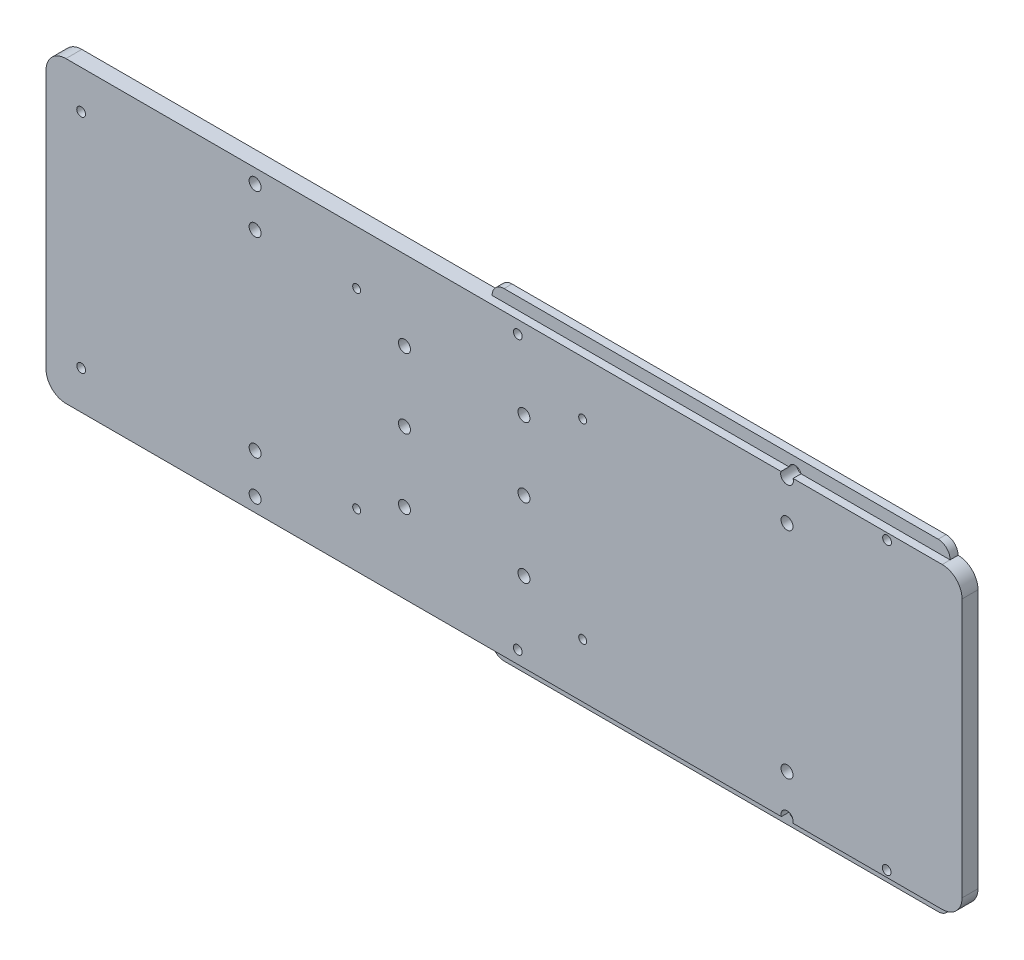
SolidWorks part; units mm, degrees
ref_plane "Plan de face" through (0, 0, 0) normal (0, 0, 1) x (1, 0, 0)
ref_plane "Plan de dessus" through (0, 0, 0) normal (0, 1, 0) x (1, 0, 0)
ref_plane "Plan de droite" through (0, 0, 0) normal (1, 0, 0) x (0, 0, -1)
sketch "Sketch1" plane through (0, 0, 0) normal (0, 0, 1) x (1, 0, 0)
  line L1 (0, 0) -> (230, 0)
  line L2 (0, 0) -> (0, 75)
  line L3 (0, 75) -> (230, 75)
  line L4 (230, 0) -> (230, 75)
  dimension "D1" = 230
  dimension "D2" = 75
extrude "Boss-Extrude1" add sketch "Sketch1" along normal blind 4
sketch "Sketch2" plane through (0, 0, 0) normal (0, 0, -1) x (-1, 0, 0)
  line L0 (-9.0685, 28.6546) -> (-9.0685, 48.2614) construction
  text T0 "BOTTOM"
extrude "Cut-Extrude1" cut sketch "Sketch2" against normal blind 1
fillet "Fillet1" radius 5 4 edges at (0, 0, 2) (230, 0, 2) (0, 75, 2) (230, 75, 2)
sketch "Sketch4" plane through (0, 0, 0) normal (0, 0, -1) x (-1, 0, 0)
  line L0 (-230, 5) -> (-230, 70) construction
  line L1 (-225, 75) -> (-110, 75)
  line L2 (-225, 75) -> (-225, 78)
  line L3 (-225, 78) -> (-110, 78)
  line L4 (-110, 75) -> (-110, 78)
  line L5 (-225, 0) -> (-110, 0)
  line L6 (-225, 0) -> (-225, -3)
  line L7 (-225, -3) -> (-110, -3)
  line L8 (-110, 0) -> (-110, -3)
  dimension "D1" = 3
  dimension "D2" = 3
  dimension "D3" = 120
  dimension "D4" = 120
extrude "Boss-Extrude2" add sketch "Sketch4" against normal blind 2 separate body
fillet "Fillet4" radius 3 1 edges at (225, 78, 1)
fillet "Fillet5" radius 3 2 edges at (110, -3, 1) (225, -3, 1)
fillet "Fillet6" radius 3 1 edges at (110, 78, 1)
sketch "Sketch5" plane through (0, 0, 0) normal (0, 0, -1) x (-1, 0, 0)
  line L0 (0, 70) -> (0, 5) construction
  line L1 (-5, 0) -> (-225, 0) construction
  line L2 (-225, 75) -> (-5, 75) construction
  line L3 (-230, 5) -> (-230, 70) construction
  line L4 (-222, -3) -> (-113, -3) construction
  line L5 (-113, 78) -> (-222, 78) construction
  circle A0 centre (-8.82, 9.65) radius 1.1
  circle A1 centre (-8.82, 65.35) radius 1.1
  circle A2 centre (-118.46, 71.81) radius 1.1
  circle A3 centre (-118.46, 3.19) radius 1.1
  circle A4 centre (-211.07, 1.6) radius 1.1
  circle A5 centre (-211.17, 73.4) radius 1.1
  dimension "D1" = 2.2
  dimension "D2" = 2.2
  dimension "D3" = 8.82
  dimension "D4" = 9.65
  dimension "D5" = 9.65
  dimension "D7" = 2.2
  dimension "D8" = 2.2
  dimension "D9" = 2.2
  dimension "D10" = 2.2
  dimension "D16" = 6.19
  dimension "D17" = 6.19
  dimension "D18" = 4.6
  dimension "D6" = 8.82
  dimension "D11" = 111.54
  dimension "D12" = 111.54
  dimension "D13" = 18.83
  dimension "D14" = 18.93
  dimension "D15" = 4.6
extrude "Cut-Extrude2" cut sketch "Sketch5" against normal through all
sketch "Sketch6" plane through (0, 0, 0) normal (0, 0, -1) x (-1, 0, 0)
  line L0 (-113, 78) -> (-222, 78) construction
  line L1 (-230, 5) -> (-230, 70) construction
  line L2 (-222, -3) -> (-113, -3) construction
  line L3 (-5, 0) -> (-225, 0) construction
  line L4 (0, 70) -> (0, 5) construction
  line L5 (-225, 75) -> (-5, 75) construction
  circle A0 centre (-52.5, 3.5) radius 1.5
  circle A1 centre (-52.5, 13.5) radius 1.5
  circle A2 centre (-52.5, 61.5) radius 1.5
  circle A3 centre (-52.5, 71.5) radius 1.5
  circle A4 centre (-186.05, 74.5) radius 1.5
  circle A5 centre (-186.05, 64.5) radius 1.5
  circle A6 centre (-186.05, 10.5) radius 1.5
  circle A7 centre (-186.05, 0.5) radius 1.5
  dimension "D1" = 3
  dimension "D2" = 3
  dimension "D3" = 3
  dimension "D4" = 3
  dimension "D5" = 3.5
  dimension "D6" = 10
  dimension "D7" = 43.95
  dimension "D8" = 43.95
  dimension "D9" = 10
  dimension "D10" = 3.5
  dimension "D11" = 3
  dimension "D12" = 3
  dimension "D13" = 3
  dimension "D14" = 3
  dimension "D15" = 3.5
  dimension "D16" = 10
  dimension "D17" = 52.5
  dimension "D18" = 10
  dimension "D19" = 3.5
extrude "Cut-Extrude3" cut sketch "Sketch6" against normal through all contours A6 | A5 | A7 | A4 region at (186.05, 74.5, 0) region at (186.05, 64.5, 0) region at (186.05, 10.5, 0) region at (186.05, 0.5, 0)
sketch "Sketch7" plane through (0, 0, 0) normal (0, 0, -1) x (-1, 0, 0)
  line L0 (-225, 75) -> (-187.4642, 75) construction
  line L1 (-5, 0) -> (-184.6358, 0) construction
  line L4 (0, 70) -> (0, 5) construction
  circle A0 centre (-120, 20) radius 1.5
  circle A1 centre (-120, 55) radius 1.5
  circle A2 centre (-90, 20) radius 1.5
  circle A3 centre (-90, 55) radius 1.5
  circle A4 centre (-90, 37.5) radius 1.5
  circle A5 centre (-120, 37.5) radius 1.5
  dimension "D1" = 3
  dimension "D2" = 3
  dimension "D3" = 3
  dimension "D4" = 3
  dimension "D5" = 3
  dimension "D6" = 3
  dimension "D7" = 20
  dimension "D8" = 20
  dimension "D9" = 20
  dimension "D10" = 20
  dimension "D11" = 30
  dimension "D12" = 90
  dimension "D13" = 17.5
extrude "Cut-Extrude4" cut sketch "Sketch7" against normal through all
sketch "Sketch8" plane through (0, 0, 0) normal (0, 0, -1) x (-1, 0, 0)
  line L0 (0, 70) -> (0, 5) construction
  line L1 (-225, 75) -> (-187.4642, 75) construction
  circle A0 centre (-78, 61.5) radius 1
  circle A1 centre (-78, 13.6) radius 1
  circle A2 centre (-134.75, 13.6) radius 1
  circle A3 centre (-134.75, 61.5) radius 1
  dimension "D1" = 2
  dimension "D2" = 2
  dimension "D3" = 2
  dimension "D4" = 2
  dimension "D5" = 78
  dimension "D7" = 13.5
  dimension "D6" = 56.75
  dimension "D8" = 47.9
extrude "Cut-Extrude5" cut sketch "Sketch8" against normal through all
extrude "Cut-Extrude6" cut sketch "Sketch6<3>" against normal blind 10
sketch "Sketch6<3>" plane through (0, 0, 0) normal (0, 0, -1) x (-1, 0, 0) same geometry as "Sketch6"
sketch "Sketch9" plane through (0, 0, 0) normal (0, 0, -1) x (-1, 0, 0)
  circle A0 centre (-186.05, 0.5) radius 1.5
  circle A1 centre (-186.05, 74.5) radius 1.6
  dimension "D1" = 3.2
extrude "Cut-Extrude7" cut sketch "Sketch9" against normal blind 10
